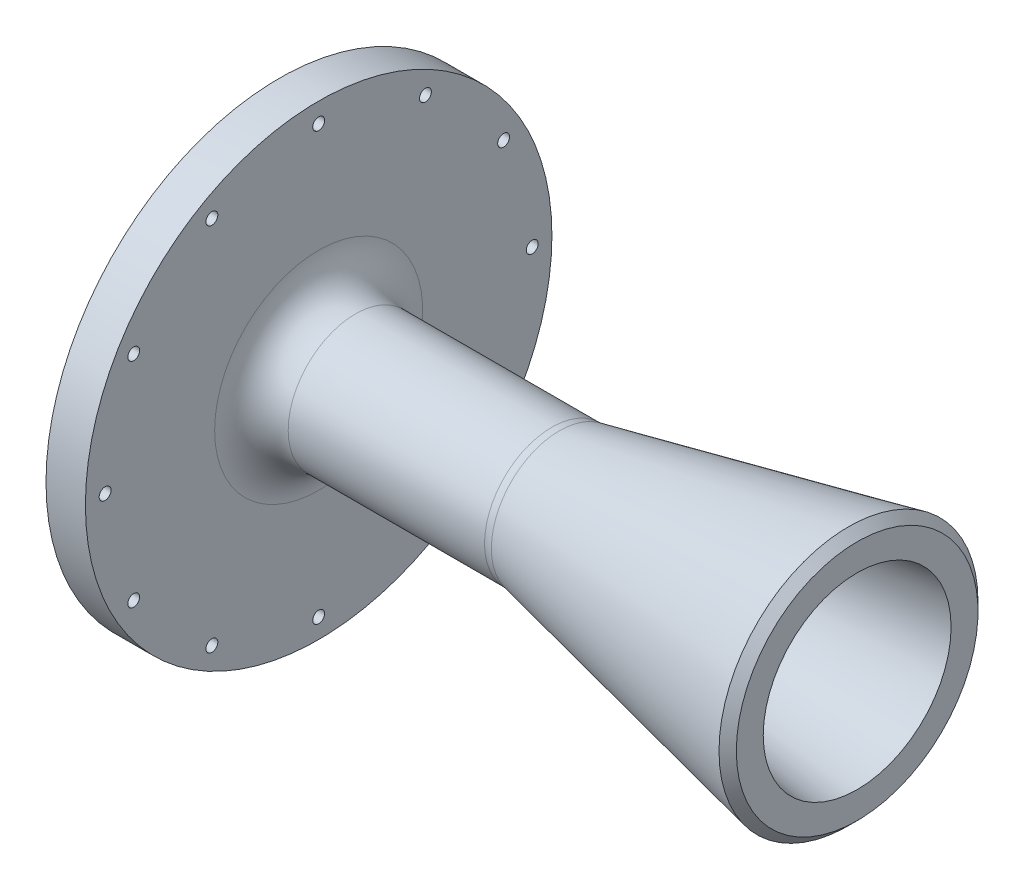
SolidWorks part; units mm, degrees
material "Stainless Steel (ferritic)"
ref_plane "Front Plane" through (0, 0, 0) normal (0, 0, 1) x (1, 0, 0)
ref_plane "Top Plane" through (0, 0, 0) normal (0, 1, 0) x (1, 0, 0)
ref_plane "Right Plane" through (0, 0, 0) normal (1, 0, 0) x (0, 0, -1)
sketch "Sketch2" plane through (0, 0, 0) normal (0, 0, 1) x (1, 0, 0)
  line L0 (0, 0) -> (165.0115, 0) construction
  line L1 (0, 20.5835) -> (0, 56.388)
  line L2 (0, 56.388) -> (9.525, 56.388)
  line L3 (9.525, 56.388) -> (9.525, 16.256)
  line L11 (66.8065, 16.256) -> (139.7, 31.75)
  line L17 (139.7, 31.75) -> (139.7, 22.7076)
  line L18 (60.325, 12.7208) -> (60.325, 14.351)
  line L19 (60.325, 14.351) -> (10.795, 14.351)
  line L20 (0, 20.5835) -> (10.795, 14.351)
  line L21 (60.325, 12.7208) -> (139.7, 22.7076)
  line L22 (9.525, 16.256) -> (66.8065, 16.256)
  point P9 (60.325, 21.7632)
  point P10 (73.6294, 20.5835)
  point P12 (25.4171, 19.5362)
  point P16 (19.05, 20.5835)
  point P17 (0, 0)
  point P18 (19.05, 17.9952)
  point P19 (9.525, 18.6212)
  point P20 (19.05, 17.0562)
  point P21 (9.525, 19.4037)
  point P22 (19.05, 17.1344)
  point P23 (9.525, 17.1108)
  point P24 (139.7, 27.94)
  point P25 (60.325, 16.0338)
  point P26 (9.525, 19.2311)
  point P27 (0, 0)
  point P28 (9.525, 17.2989)
  point P29 (60.325, 17.2989)
  point P30 (9.525, 18.5441)
  point P31 (9.525, 18.2009)
  point P32 (60.325, 16.1551)
  point P33 (9.525, 17.2885)
  point P34 (67.6967, 16.9224)
  dimension "D2" = 9.525
  dimension "D3" = 1.905
  dimension "D4" = 10.795
  dimension "D5" = 14.351
  dimension "D6" = 31.75
  dimension "D7" = 7.171
  dimension "D8" = 139.7
  dimension "D9" = 22.7076
  dimension "D10" = 30
  dimension "D11" = 56.388
  dimension "D12" = 49.53
  dimension "D13" = 12
revolve "Main Structure" add sketch "Sketch2" angle 360 about L0
sketch "Sketch4" plane through (0, 0, 0) normal (-1, 0, 0) x (0, 0, 1)
  circle A0 centre (0, 0) radius 51.6255 construction
  circle A1 centre (0, -51.6255) radius 2.146
  circle A2 centre (-25.8127, -44.709) radius 2.146
  circle A3 centre (-44.709, -25.8128) radius 2.146
  circle A4 centre (-51.6255, 0) radius 2.146
  circle A5 centre (-44.709, 25.8127) radius 2.146
  circle A6 centre (-25.8128, 44.709) radius 2.146
  circle A7 centre (0, 51.6255) radius 2.146
  circle A8 centre (25.8127, 44.709) radius 2.146
  circle A9 centre (44.709, 25.8128) radius 2.146
  circle A10 centre (51.6255, 0) radius 2.146
  circle A11 centre (44.709, -25.8127) radius 2.146
  circle A12 centre (25.8128, -44.709) radius 2.146
  point P29 (0, 0)
  dimension "D1" = 12
  dimension "D2" = 103.251
hole_wizard "Flange Holes" positions "Sketch7" profile "Sketch8" hole size "#33" standard "ANSI Inch" end condition up to next
sketch "Sketch7" plane through (0, 0, 0) normal (-1, 0, 0) x (0, 0, 1)
  point P0 (0, -51.6255)
  point P3 (-25.8127, -44.709)
  point P6 (-44.709, -25.8128)
  point P9 (-51.6255, 0)
  point P12 (-44.709, 25.8127)
  point P15 (-25.8128, 44.709)
  point P18 (0, 51.6255)
  point P21 (25.8127, 44.709)
  point P24 (44.709, 25.8128)
  point P27 (51.6255, 0)
  point P30 (44.709, -25.8127)
  point P33 (25.8128, -44.709)
sketch "Sketch8" plane through (0, -51.6255, 0) normal (0, 1, 0) x (0, 0, 1)
  line L0 (0, 0) -> (0, 9.525)
  line L1 (0, 9.525) -> (1.4351, 9.525)
  line L2 (1.4351, 9.525) -> (1.4351, 0)
  line L5 (1.4351, 0) -> (0, 0)
  line L11 (0, -6.35) -> (0, 107.95) construction
  dimension "Thru Hole Dia." = 2.8702
  dimension "Thru Hole Depth" = 9.525
sketch "Sketch9" plane through (0, 0, 0) normal (-1, 0, 0) x (0, 0, 1)
  line L0 (0, 0) -> (-67.6727, 18.1329) construction
  line L1 (0, 0) -> (-51.6255, 0) construction
  circle A0 centre (0, 0) radius 51.6255 construction
  circle A1 centre (-49.8664, 13.3617) radius 2.9451
  circle A2 centre (49.8664, -13.3617) radius 2.9451
  point P14 (0, 0)
  dimension "D1" = 15
  dimension "D2" = 2
hole_wizard "Dowel Holes" positions "Sketch10" profile "Sketch11" hole size "3/16" standard "ANSI Inch"
sketch "Sketch10" plane through (0, 0, 0) normal (-1, 0, 0) x (0, 0, 1)
  point P0 (49.8664, -13.3617)
  point P3 (-49.8664, 13.3617)
sketch "Sketch11" plane through (0, -13.3617, 49.8664) normal (0, 1, 0) x (0, 0, 1)
  line L0 (0, 0) -> (0, 7.7808)
  line L1 (0, 7.7808) -> (2.3812, 6.35)
  line L2 (2.3812, 6.35) -> (2.3812, 0)
  line L5 (2.3812, 0) -> (0, 0)
  line L10 (0, 7.7808) -> (-2.3812, 6.35) construction
  line L11 (0, -6.35) -> (0, 107.95) construction
  dimension "Hole Dia." = 4.7625
  dimension "Hole Depth" = 6.35
  dimension "Drill Angle" = 118
fillet "Fillet1" radius 8.89 2 edges at (66.8065, 0, 16.256) (9.525, 0, 16.256)
sketch "Sketch13" plane through (0, 0, 0) normal (0, 1, 0) x (1, 0, 0)
  line L0 (0, 38.1) -> (3.3333, 0)
  line L1 (0, 56.388) -> (0, -56.388) construction
  line L2 (3.3333, 0) -> (0, 0)
  line L3 (0, 0) -> (0, 38.1)
  dimension "D1" = 38.1
  dimension "D2" = 5
revolve "Cut-Revolve1" cut sketch "Sketch13" angle 360 about L2
chamfer "Chamfer1" distance 2.54 angle 45 1 edges at (139.7, 0, 31.75) first distance on face at (139.7, 0, 31.75)
